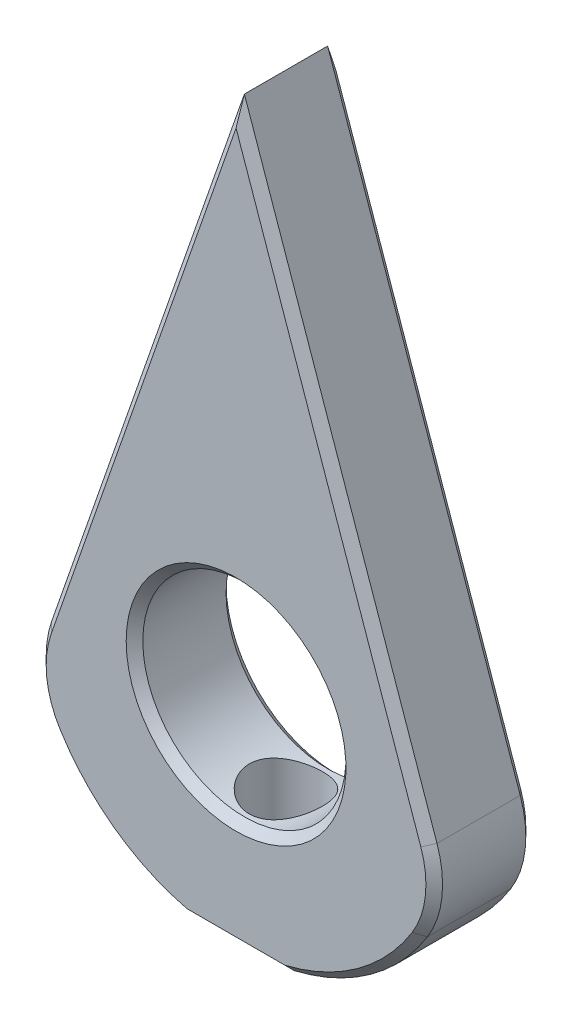
SolidWorks part; units mm, degrees
ref_plane "Front" through (0, 0, 0) normal (0, 0, 1) x (1, 0, 0)
ref_plane "Top" through (0, 0, 0) normal (0, 1, 0) x (1, 0, 0)
ref_plane "Right" through (0, 0, 0) normal (1, 0, 0) x (0, 0, -1)
sketch "Skizze1" plane through (0, 0, 0) normal (0, 0, 1) x (1, 0, 0)
  line L0 (0, 0) -> (0, 20.0957) construction
  line L3 (0, 0) -> (0, -13.0268) construction
  line L4 (-3, -12.6) -> (3, -12.6)
  line L5 (12.3451, -3.9191) -> (0, 31.5)
  line L6 (-12.3451, -3.9191) -> (0, 31.5)
  circle A0 centre (0, 0) radius 6.1
  arc A2 (3, -12.6) -> (12.3451, -3.9191) centre (0, 0) ccw
  arc A3 (-3, -12.6) -> (-12.3451, -3.9191) centre (0, 0) cw
  point P8 (0, -6.1)
  point P9 (0, -12.6)
  point P12 (12.5786, -2.6914)
  point P13 (12.0764, -4.5458)
  point P14 (12.2987, -3.9044)
  point P15 (0, 28.7759)
  point P16 (0, 30.044)
  dimension "D1" = 12.2
  dimension "D2" = 6.5
  dimension "D3" = 6
  dimension "D4" = 31.5
extrude "Aufsatz-Linear austragen1" add sketch "Skizze1" along normal blind 6
sketch "Skizze2" plane through (0, -12.6, 0) normal (0, -1, 0) x (1, 0, 0)
  line L0 (0, 0) -> (0, 6) construction
  line L1 (-3, 0) -> (3, 0) construction
  line L2 (-3, 6) -> (3, 6) construction
  circle A0 centre (0, 3) radius 2.2
  dimension "D1" = 4.4
extrude "Schnitt-Linear austragen1" cut sketch "Skizze2" against normal up to next
fillet "Verrundung1" radius 6 2 edges at (12.3451, -3.9191, 3) (-12.3451, -3.9191, 3)
chamfer "Fase1" distance 0.5 angle 45 16 edges at (6.1, 0, 0) (0, -12.6, 0) (7.5697, -10.51, 0) (5.785, 14.9022, 0) (-5.785, 14.9022, 0) (-7.5697, -10.51, 0) (6.1, 0, 6) (-5.785, 14.9022, 6) (5.785, 14.9022, 6) (7.5697, -10.51, 6) (0, -12.6, 6) (-7.5697, -10.51, 6) (-11.8679, -4.3314, 0) (11.8679, -4.3314, 0) (-11.8679, -4.3314, 6) (11.8679, -4.3314, 6)
